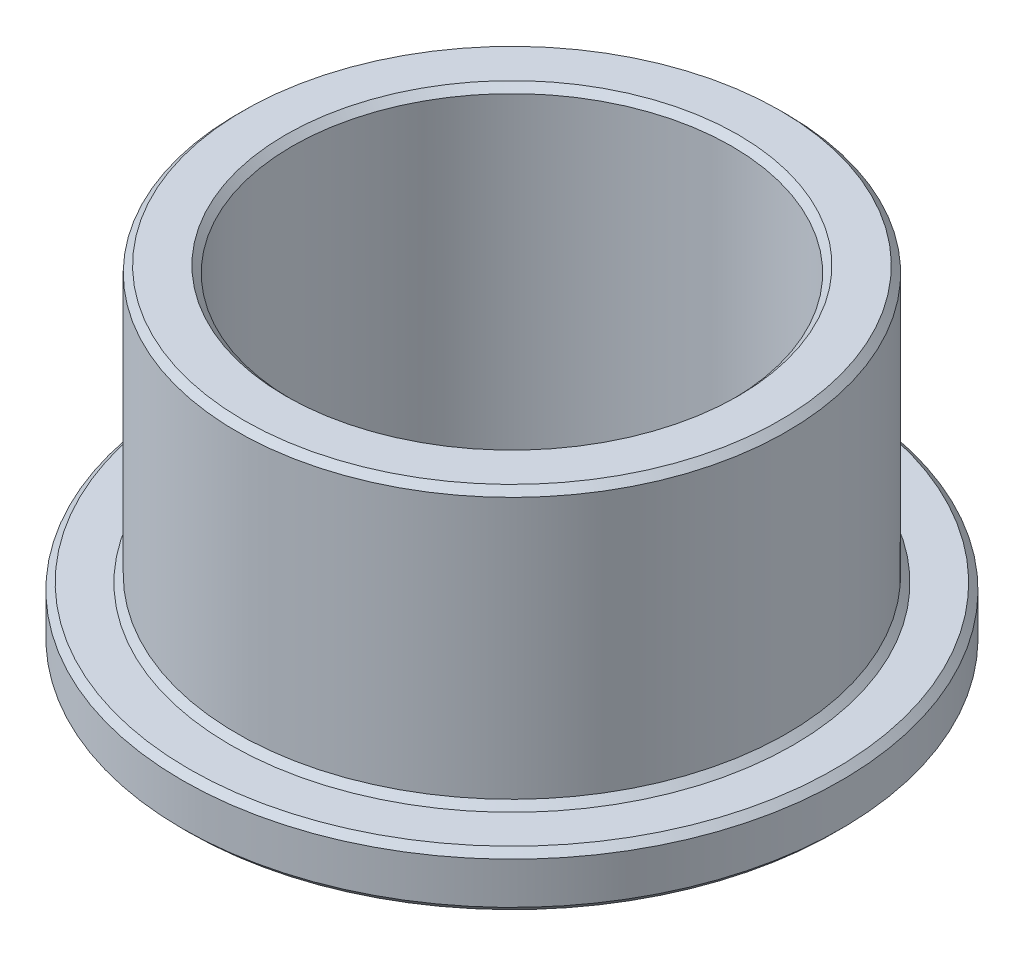
SolidWorks part; units mm, degrees
ref_plane "Front Plane" through (0, 0, 0) normal (0, 0, 1) x (1, 0, 0)
ref_plane "Top Plane" through (0, 0, 0) normal (0, 1, 0) x (1, 0, 0)
ref_plane "Right Plane" through (0, 0, 0) normal (1, 0, 0) x (0, 0, -1)
sketch "Sketch1" plane through (0, 0, 0) normal (0, 1, 0) x (1, 0, 0)
  circle A0 centre (-30.3855, 94.9078) radius 12.7
  circle A1 centre (-30.3855, 94.9078) radius 15.8877
  circle A2 centre (-30.3855, 94.9078) radius 19.05
extrude "Boss-Extrude1" add sketch "Sketch1" along normal blind 3.175 contours A2 A1 region at (-48.8967, 0, -94.9078)
extrude "Boss-Extrude2" add sketch "Sketch1<3>" along normal blind 19.05 contours A1 A0 region at (-45.8238, 0, -94.9078)
sketch "Sketch1<3>" plane through (0, 0, 0) normal (0, 1, 0) x (1, 0, 0) same geometry as "Sketch1"
chamfer "Chamfer1" distance 0.381 angle 45 6 edges at (-30.3855, 0, -82.2078) (-30.3855, 0, -75.8578) (-30.3855, 3.175, -75.8578) (-30.3855, 3.175, -79.0201) (-30.3855, 19.05, -82.2078) (-30.3855, 19.05, -79.0201)
